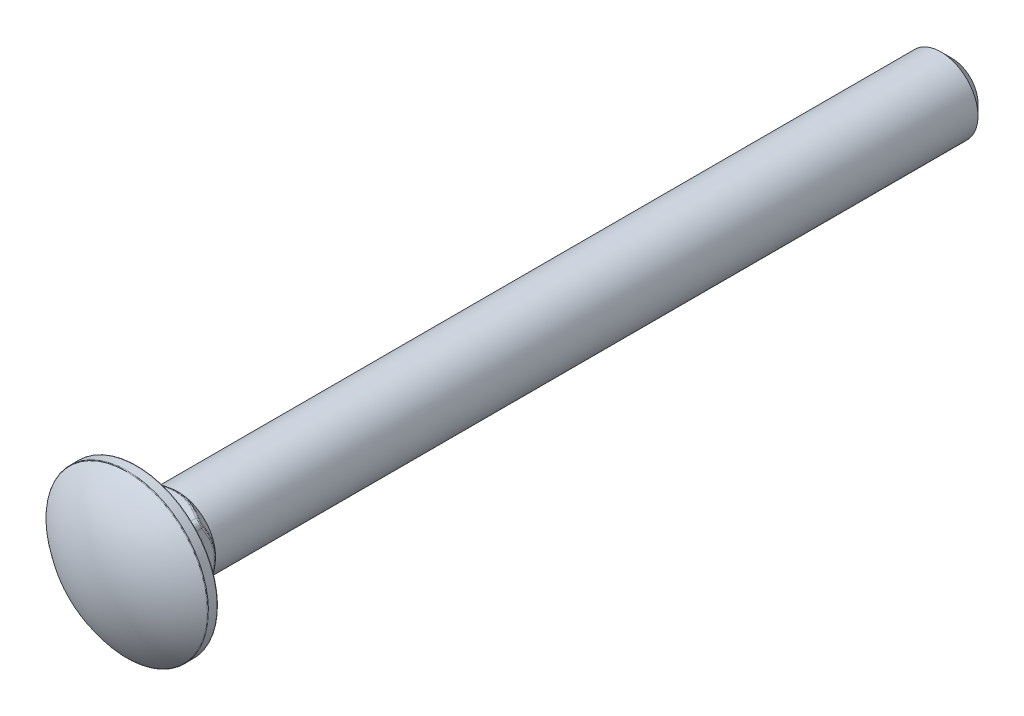
SolidWorks part; units mm, degrees
ref_plane "Front Plane" through (0, 0, 0) normal (0, 0, 1) x (1, 0, 0)
ref_plane "Top Plane" through (0, 0, 0) normal (0, 1, 0) x (1, 0, 0)
ref_plane "Right Plane" through (0, 0, 0) normal (1, 0, 0) x (0, 0, -1)
sketch "Sketch1" plane through (0, 0, 0) normal (1, 0, 0) x (0, 0, -1)
  line L0 (-66.421, 0) -> (73.279, 0) construction
  line L1 (73.279, -6.35) -> (73.279, 6.35) construction
  line L2 (73.279, 6.35) -> (71.3252, 6.35) construction
  line L3 (-66.421, 0) -> (-73.279, 0) construction
  line L4 (-66.421, -13.8938) -> (-66.421, 13.8938) construction
  line L6 (73.279, -6.35) -> (68.3944, -6.35) construction
  line L7 (-73.279, 0) -> (73.279, 0) construction
  line L8 (73.279, 6.35) -> (-59.309, 6.35) construction
  line L9 (-59.309, 6.604) -> (-59.309, -6.604) construction
  point P4 (-59.309, 0)
  point P13 (-66.421, 0)
  point P14 (-59.309, 0)
  point P16 (-73.279, 0)
  point P19 (68.3944, -6.35)
  dimension "D3" = 4.8846
sketch "Sketch3" plane through (0, 0, 0) normal (1, 0, 0) x (0, 0, -1)
  line L0 (-73.279, 0) -> (73.279, 0)
  line L1 (73.279, 0) -> (73.279, 6.35)
  line L2 (73.279, 6.35) -> (-66.421, 6.35)
  line L3 (-66.421, -13.8938) -> (-66.421, 13.8938) construction
  line L8 (-66.421, 13.8938) -> (-68.1355, 13.8938)
  line L9 (-66.421, 6.35) -> (-66.421, 13.8938)
  arc A0 (-73.279, 0) -> (-68.1355, 13.8938) centre (-51.942, 0) cw
  dimension "D1" = 1.7145
revolve "Revolve1" add sketch "Sketch3" angle 360 about L0
chamfer "Chamfer1" distance 1.905 angle 45 1 edges at (0, -6.35, -73.279)
sketch "Sketch8" plane through (0, 0, 66.421) normal (0, 0, -1) x (-1, 0, 0)
  line L0 (0, 6.604) -> (0, -6.604) construction
  line L1 (6.604, -6.604) -> (-6.604, -6.604)
  line L2 (6.604, -6.604) -> (6.604, 6.604)
  line L3 (6.604, 6.604) -> (-6.604, 6.604)
  line L4 (-6.604, -6.604) -> (-6.604, 6.604)
  line L5 (6.604, -6.604) -> (-6.604, 6.604) construction
  line L6 (6.604, 6.604) -> (-6.604, -6.604) construction
  point P0 (0, 0)
extrude "Boss-Extrude2" add sketch "Sketch8" along normal up to vertex (7.112 mm away) separate body up to point (0, 0, 59.309)
sketch "Sketch9" plane through (0, 0, 59.309) normal (0, 0, -1) x (-1, 0, 0)
  circle A0 centre (0, 0) radius 6.35
extrude "Cut-Extrude1" cut sketch "Sketch9" against normal through all draft 45 flip side to cut
combine bodies "Combine1" operation type add bodies to combine 104 121
fillet "Fillet2" radius 0.9906 4 edges at (-6.604, 6.604, 64.3597) (-6.604, -6.604, 64.3597) (6.604, -6.604, 64.3597) (6.604, 6.604, 64.3597)
fillet "Fillet3" radius 0.6604 8 edges at (6.3139, 6.3139, 66.421) (0, 6.604, 66.421) (-6.3139, 6.3139, 66.421) (-6.604, 0, 66.421) (-6.3139, -6.3139, 66.421) (0, -6.604, 66.421) (6.3139, -6.3139, 66.421) (6.604, 0, 66.421)
fillet "Fillet4" radius 0.1715 2 edges at (0, -13.8938, 66.421) (0, -13.8938, 68.1355)
fillet "Fillet5" radius 0.508 8 edges at (-6.3577, -6.267, 61.8863) (-1.7765, -6.604, 59.7978) (6.267, -6.3577, 61.8863) (6.604, -1.7765, 59.7978) (6.3577, 6.267, 61.8863) (-1.7765, 6.604, 59.7978) (-6.267, 6.3577, 61.8863) (-6.604, -1.7765, 59.7978)
ref_plane "Plane2" through (0, 0, 73.279) normal (0, 0, 1) x (1, 0, 0)
ref_plane "Plane3" through (0, 0, 59.309) normal (0, 0, 1) x (1, 0, 0)
sketch "Sketch10" plane through (0, 0, -73.279) normal (0, 0, -1) x (-1, 0, 0)
  circle A0 centre (0, 0) radius 6.35
curve "Helix/Spiral2" pitch 1.9538 height 132.588 turns 67.86
sketch "Reference Sketch1" plane through (0, 0, 0) normal (0, 0, 1) x (1, 0, 0)
  line L4 (-6.604, -6.604) -> (6.604, -6.604)
  line L5 (6.604, -6.604) -> (6.604, 6.604)
  line L6 (6.604, 6.604) -> (-6.604, 6.604)
  line L7 (-6.604, 6.604) -> (-6.604, -6.604)
  line L8 (-6.604, -6.604) -> (6.604, -6.604) construction
  line L9 (6.604, -6.604) -> (6.604, 6.604) construction
  line L10 (6.604, 6.604) -> (-6.604, 6.604) construction
  line L11 (-6.604, 6.604) -> (-6.604, -6.604) construction
  circle A0 centre (0, 0) radius 13.8938 construction
  dimension "D1" = 0
ref_plane "Plane1" [suppressed] through (0, 0, 59.309) normal (0, 0, 1) x (1, 0, 0)
split "Split1" [suppressed] bodies to split 122 104
sketch "Sketch4" [suppressed] plane through (0, 0, -73.279) normal (0, 0, -1) x (-1, 0, 0)
  circle A0 centre (0, 0) radius 6.35 construction
  circle A3 centre (0, 0) radius 6.35
curve "Helix/Spiral1" [suppressed] pitch 1.9538 height 82.0615 turns 42
sketch "Sketch6" [suppressed] plane through (0, 0, 0) normal (1, 0, 0) x (0, 0, -1)
  line L0 (73.1569, 6.5615) -> (74.1338, 4.8694) construction
  line L1 (74.1338, 4.8694) -> (75.1107, 6.5615) construction
  line L2 (75.1107, 6.5615) -> (73.1569, 6.5615) construction
  line L3 (73.2179, 6.4558) -> (75.0497, 6.4558)
  line L4 (73.2179, 6.4558) -> (75.0497, 6.4558) construction
  line L5 (74.0117, 5.0809) -> (74.2559, 5.0809)
  line L6 (74.1338, 5.0809) -> (74.1338, 4.8694) construction
  line L7 (74.1338, 6.5615) -> (74.1338, 6.35) construction
  line L8 (73.2179, 6.4558) -> (74.0117, 5.0809)
  line L9 (74.2559, 5.0809) -> (75.0497, 6.4558)
  line L10 (73.279, 6.35) -> (71.3252, 6.35) construction
  line L11 (73.279, 6.35) -> (74.9886, 6.35) construction
  line L13 (73.279, -6.35) -> (73.279, 6.35)
  line L14 (73.279, -6.35) -> (73.279, 6.35) construction
  point P13 (74.1338, 6.4558)
  dimension "D2" = 0.2442
sweep "Cut-Sweep1" [suppressed] cut profiles "Sketch6" path "Helix/Spiral1"
pattern_linear "LPattern1" [suppressed] count 2 spacing 78.1538 along (0, 0, 1) of bodies 109
sketch "Sketch7" [suppressed] plane through (0, 0, 59.309) normal (0, 0, 1) x (1, 0, 0)
  circle A1 centre (0, 0) radius 6.35
  circle A2 centre (0, 0) radius 6.35
  dimension "D1" = 0
extrude "Boss-Extrude1" [suppressed] add sketch "Sketch7" against normal through all draft 44.052
equation "\"D4@Helix/Spiral1\" = \"Thread Pitch@Sketch1\""
equation "\"D3@Helix/Spiral1\"=\"Segment Length\"+\"Thread Pitch@Sketch1\""
equation "\"D1@Chamfer1\"=\"Thread Diameter@Sketch1\"*0.15"
equation "\"D2@Sketch6\"= \"Thread Pitch@Sketch1\" / 8"
equation "\"D3@Sketch1\"=\"Thread Pitch@Sketch1\"*2.5"
equation "\"D3@LPattern1\"=\"Segment Length\"-\"Thread Pitch@Sketch1\""
equation "\"Thread Count\"= ( \"Length@Sketch1\" - \"Neck Length@Sketch1\" ) * 0.6 / \"Thread Pitch@Sketch1\""
equation "\"Rounded Thread Count\"= IIF ( \"Thread Count\" - int ( \"Thread Count\" ) > 0 , int ( \"Thread Count\" ) + 1 , \"Thread Count\" )"
equation "\"Segment Length\"= \"Thread Pitch@Sketch1\" * \"Rounded Thread Count\""
equation "\"D3@Boss-Extrude1\"=\"Taper Angle\""
equation "\"Pitch Natural Taper Angle\"= ATN ( \"Thread Pitch@Sketch1\" / 2 )"
equation "\"Angle Count\"= 45 / \"Pitch Natural Taper Angle\""
equation "\"Rounded Angle Count\"= ROUND ( \"Angle Count\" )"
equation "\"Taper Angle\"= \"Rounded Angle Count\" * \"Pitch Natural Taper Angle\""
equation "\"D1@Sketch3\"=\"Head Height@Sketch1\"*0.25"
equation "\"D1@Fillet2\"=\"Neck Width@Sketch1\"*0.075"
equation "\"D1@Fillet3\"=\"Neck Width@Sketch1\"*0.05"
equation "\"D1@Fillet4\"=\"Head Height@Sketch1\"*0.025"
equation "\"D1@Fillet5\"=abs( \"Neck Width@Sketch1\"-\"Thread Diameter@Sketch1\")"
equation "\"D3@Helix/Spiral2\" = \"Length@Sketch1\" - \"Neck Length@Sketch1\""
equation "\"D4@Helix/Spiral2\"= \"Thread Pitch@Sketch1\""
